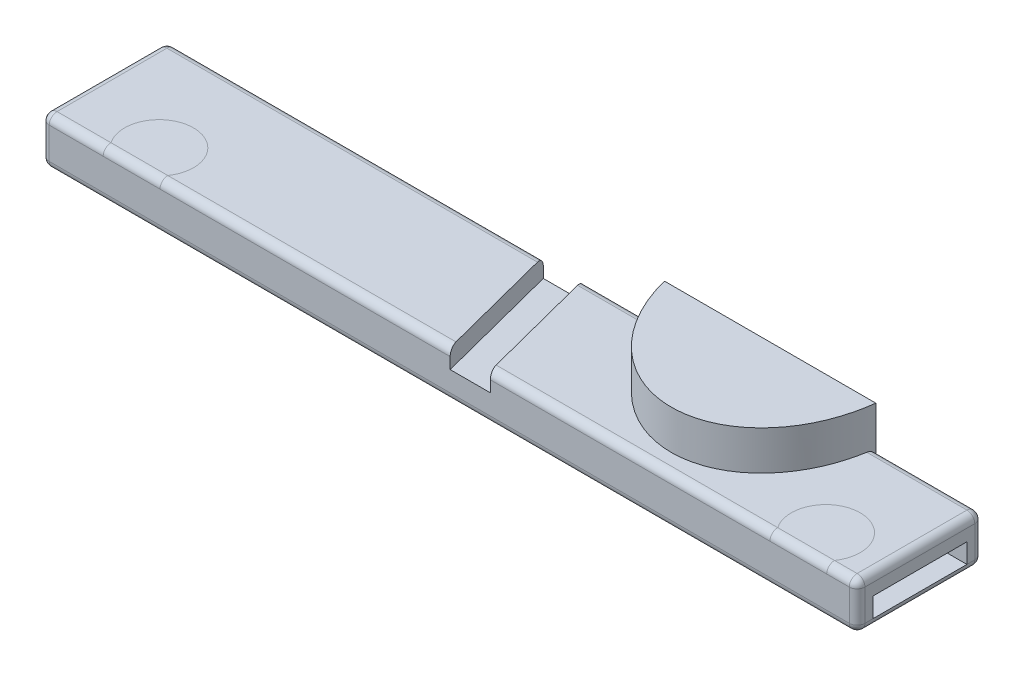
SolidWorks part; units mm, degrees
material "Wood floor laminate, Egger MED"
ref_plane "Front Plane" through (0, 0, 0) normal (0, 0, 1) x (1, 0, 0)
ref_plane "Top Plane" through (0, 0, 0) normal (0, 1, 0) x (1, 0, 0)
ref_plane "Right Plane" through (0, 0, 0) normal (1, 0, 0) x (0, 0, -1)
sketch "Sketch1" plane through (0, 0, 0) normal (0, 1, 0) x (1, 0, 0)
  line L1 (-139.7, -31.75) -> (139.7, -31.75)
  line L2 (-139.7, -31.75) -> (-139.7, 31.75)
  line L3 (-139.7, 31.75) -> (139.7, 31.75)
  line L4 (139.7, -31.75) -> (139.7, 31.75)
  line L5 (-139.7, -31.75) -> (139.7, 31.75) construction
  line L6 (-139.7, 31.75) -> (139.7, -31.75) construction
  point P0 (0, 0)
  dimension "D1" = 279.4
  dimension "D2" = 63.5
extrude "Boss-Extrude1" add sketch "Sketch1" along normal blind 12.7
sketch "Sketch2" plane through (0, 12.7, 0) normal (0, 1, 0) x (1, 0, 0)
  line L0 (-47.7, -21.75) -> (-28.3351, -16.75)
  line L1 (-139.7, 31.75) -> (-139.7, -31.75) construction
  line L2 (-139.7, -31.75) -> (139.7, -31.75) construction
  line L3 (-47.7, -21.75) -> (-63.575, 39.7336)
  line L8 (-63.575, 39.7336) -> (-44.2101, 44.7336)
  line L9 (-44.2101, 44.7336) -> (-28.3351, -16.75)
  line L10 (8.5141, 43.7336) -> (24.3891, -17.75)
  line L11 (24.3891, -17.75) -> (43.754, -12.75)
  line L12 (43.754, -12.75) -> (27.879, 48.7336)
  line L13 (27.879, 48.7336) -> (8.5141, 43.7336)
  dimension "D1" = 92
  dimension "D2" = 10
  dimension "D3" = 20
  dimension "D4" = 15
  dimension "D5" = 63.5
  dimension "D6" = 63.5
  dimension "D7" = 20
  dimension "D8" = 50.8
  dimension "D9" = 14
  dimension "D10" = 63.5
  dimension "D11" = 20
extrude "Boss-Extrude2" add sketch "Sketch2" along normal blind 50.8
sketch "Sketch4" plane through (-13.5914, 0, -52.6393) normal (-0.25, 0, -0.9682) x (-0.9682, 0, 0.25)
  line L0 (-143.2014, 0) -> (127.3264, 0) construction
  line L1 (0.4134, 12.7) -> (13, 12.7)
  line L2 (0.4134, 12.7) -> (0.4134, 6.5279)
  line L3 (0.4134, 6.5279) -> (13, 6.5279)
  line L4 (13, 12.7) -> (13, 6.5279)
  line L5 (-143.2014, 12.7) -> (-143.2014, 0) construction
  dimension "D1" = 13
  dimension "D2" = 6.1721
  dimension "D3" = 12.7
  dimension "D4" = 143.6148
extrude "Cut-Extrude1" cut sketch "Sketch4" against normal through all
sketch "Sketch5" plane through (-30.6187, 0, 7.9057) normal (0.9682, 0, -0.25) x (-0.25, 0, -0.9682)
  line L1 (54.3657, 12.7) -> (-23.2836, 12.7)
  line L2 (54.3657, 12.7) -> (54.3657, 63.5)
  line L3 (54.3657, 63.5) -> (-23.2836, 63.5)
  line L4 (-23.2836, 12.7) -> (-23.2836, 63.5)
extrude "Cut-Extrude2" cut sketch "Sketch5" against normal through all both and the other way through all
sketch "Sketch6" plane through (0, 12.7, 0) normal (0, 1, 0) x (1, 0, 0)
  line L0 (16.7753, 35.7864) -> (85.6147, 47.625)
  line L1 (139.7, 31.75) -> (-8.6247, 31.75) construction
  ellipse E0 centre (51.195, 41.7057) end of major axis (58.7287, -2.1012) minor radius 34.925 (16.7753, 35.7864) -> (85.6147, 47.625) ccw
  dimension "D1" = 25.4
  dimension "D2" = 69.85
  dimension "D3" = 15.875
  dimension "D4" = 44.45
  dimension "D5" = 59.8197
extrude "Boss-Extrude3" add sketch "Sketch6" along normal blind 12.7
sketch "Sketch12" plane through (0, 12.7, 0) normal (0, 1, 0) x (1, 0, 0)
  line L0 (139.7, 31.75) -> (86.0547, 31.75) construction
  circle A0 centre (-114.3, 0) radius 11.176
  circle A1 centre (101.6, 0) radius 11.176
  dimension "D1" = 22.352
  dimension "D2" = 22.352
  dimension "D6" = 31.75
  dimension "D3" = 101.6
  dimension "D4" = 114.3
  dimension "D5" = 215.9
split line "Split Line5"
sketch "Sketch17" plane through (139.7, 0, 0) normal (1, 0, 0) x (0, 0, -1)
  line L1 (26.67, 0) -> (-3.81, 0)
  line L2 (26.67, 0) -> (26.67, 6.35)
  line L3 (26.67, 6.35) -> (-3.81, 6.35)
  line L4 (-3.81, 0) -> (-3.81, 6.35)
  line L6 (-31.75, 12.7) -> (31.75, 12.7) construction
  line L8 (31.75, 12.7) -> (31.75, 0) construction
  dimension "D1" = 6.35
  dimension "D2" = 6.35
  dimension "D3" = 30.48
  dimension "D4" = 35.56
extrude "Cut-Extrude4" cut sketch "Sketch17" against normal blind 57.15
sketch "Sketch22" plane through (0, 12.7, 0) normal (0, 1, 0) x (1, 0, 0)
  line L0 (139.7, 31.75) -> (86.0547, 31.75) construction
  line L1 (139.7, -32.2049) -> (120.65, -32.2049)
  line L2 (139.7, -32.2049) -> (139.7, 31.75)
  line L3 (139.7, 31.75) -> (120.65, 31.75)
  line L4 (120.65, -32.2049) -> (120.65, 31.75)
  line L5 (139.7, -31.75) -> (139.7, 31.75) construction
  dimension "D1" = 19.05
  dimension "D2" = 19.05
  dimension "D3" = 63.9549
extrude "Cut-Extrude5" cut sketch "Sketch22" against normal through all
sketch "Sketch23" plane through (0, 0, 0) normal (0, -1, 0) x (1, 0, 0)
  line L1 (-139.7, 31.75) -> (120.65, 31.75)
  line L2 (-139.7, 31.75) -> (-139.7, -31.75)
  line L3 (-139.7, -31.75) -> (120.65, -31.75)
  line L4 (120.65, 31.75) -> (120.65, -31.75)
extrude "Boss-Extrude4" add sketch "Sketch23" along normal blind 2.54
sketch "Sketch25" plane through (0, 12.7, 0) normal (0, -1, 0) x (1, 0, 0)
  line L4 (86.0547, -31.75) -> (17.6221, -31.75)
  line L5 (16.7753, -35.7864) -> (85.6147, -47.625)
  line L6 (86.0547, -31.75) -> (17.6221, -31.75)
  line L7 (16.7753, -35.7864) -> (85.6147, -47.625)
  ellipse E4 centre (51.195, -41.7057) end of major axis (58.7287, 2.1012) minor radius 34.925 (85.6147, -47.625) -> (86.0547, -31.75) ccw
  ellipse E5 centre (51.195, -41.7057) end of major axis (58.7287, 2.1012) minor radius 34.925 (17.6221, -31.75) -> (16.7753, -35.7864) ccw
  ellipse E6 centre (51.195, -41.7057) end of major axis (58.7287, 2.1012) minor radius 34.925 (85.6147, -47.625) -> (86.0547, -31.75) ccw
  ellipse E7 centre (51.195, -41.7057) end of major axis (58.7287, 2.1012) minor radius 34.925 (17.6221, -31.75) -> (16.7753, -35.7864) ccw
  dimension "D1" = 0
extrude "Cut-Extrude6" cut sketch "Sketch25" against normal through all
sketch "Sketch27" plane through (0, 12.7, 0) normal (0, 1, 0) x (1, 0, 0)
  line L1 (-152.5085, -53.9261) -> (133.9507, -53.9261)
  line L2 (-152.5085, -53.9261) -> (-152.5085, -8.89)
  line L3 (-152.5085, -8.89) -> (133.9507, -8.89)
  line L4 (133.9507, -53.9261) -> (133.9507, -8.89)
  dimension "D1" = 286.4592
  dimension "D2" = 45.0361
  dimension "D3" = 5.08
extrude "Cut-Extrude7" cut sketch "Sketch27" against normal through all
sketch "Sketch31" plane through (-139.7, 0, 0) normal (-1, 0, 0) x (0, 0, 1)
  line L8 (-31.75, -2.54) -> (8.89, -2.54)
  line L9 (8.89, -2.54) -> (8.89, 12.7)
  line L10 (8.89, 12.7) -> (-31.75, 12.7)
  line L11 (-31.75, 12.7) -> (-31.75, -2.54)
  line L12 (-31.75, -2.54) -> (8.89, -2.54)
  line L13 (8.89, -2.54) -> (8.89, 12.7)
  line L14 (8.89, 12.7) -> (-31.75, 12.7)
  line L15 (-31.75, 12.7) -> (-31.75, -2.54)
  dimension "D1" = 0
extrude "Boss-Extrude6" add sketch "Sketch31" along normal blind 3.81
sketch "Sketch32" plane through (-143.51, 0, 0) normal (-1, 0, 0) x (0, 0, 1)
  line L0 (8.89, 12.7) -> (-31.75, 12.7) construction
  line L1 (-26.67, 6.35) -> (3.81, 6.35)
  line L2 (-26.67, 6.35) -> (-26.67, 0)
  line L3 (-26.67, 0) -> (3.81, 0)
  line L4 (3.81, 6.35) -> (3.81, 0)
  line L5 (-31.75, 12.7) -> (-31.75, -2.54) construction
  dimension "D1" = 30.48
  dimension "D2" = 6.35
  dimension "D3" = 6.35
  dimension "D4" = 35.56
extrude "Cut-Extrude10" cut sketch "Sketch32" against normal blind 38.1
fillet "Fillet3" radius 2.54 17 edges at (114.5114, 12.7, 8.89) (48.3478, 12.7, 8.89) (-59.3291, 12.7, 8.89) (-132.2914, 12.7, 8.89) (120.65, -2.54, -11.43) (-143.51, 5.08, 8.89) (-143.51, 5.08, -31.75) (120.65, 5.08, -31.75) (120.65, 5.08, 8.89) (-11.43, -2.54, -31.75) (-11.43, -2.54, 8.89) (-143.51, -2.54, -11.43) (120.65, 12.7, -11.43) (103.3524, 12.7, -31.75) (4.4987, 12.7, -31.75) (-143.51, 12.7, -11.43) (-82.5671, 12.7, -31.75)
